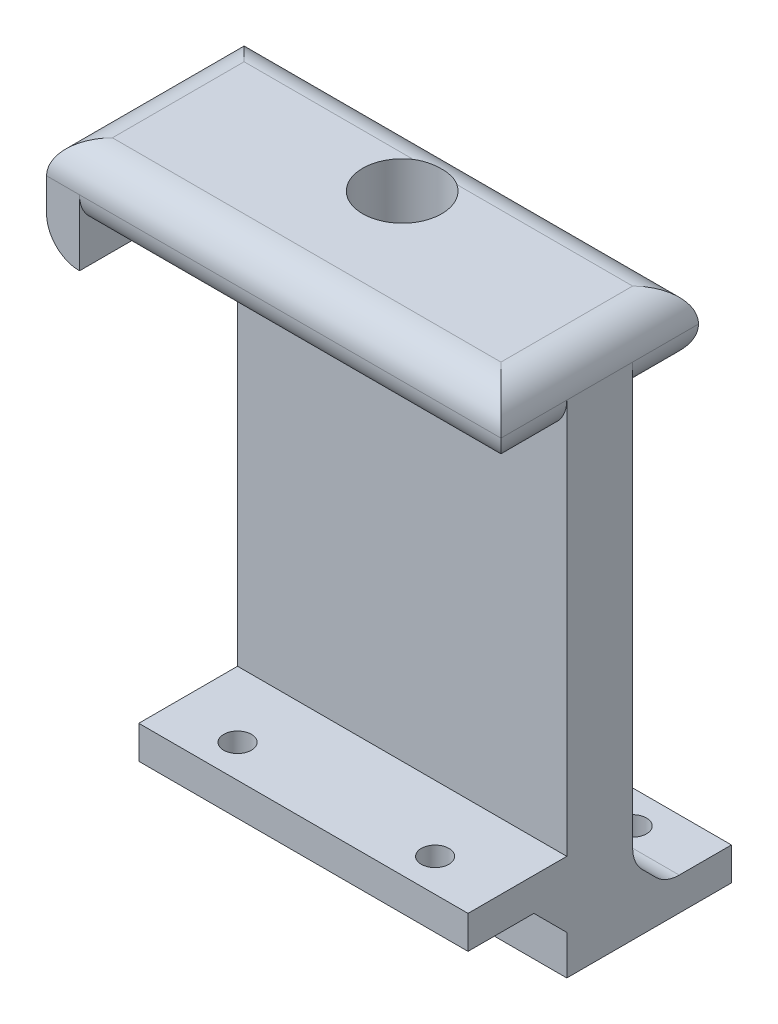
SolidWorks part; units mm, degrees
ref_plane "Plan de face" through (0, 0, 0) normal (0, 0, 1) x (1, 0, 0)
ref_plane "Plan de dessus" through (0, 0, 0) normal (0, 1, 0) x (1, 0, 0)
ref_plane "Plan de droite" through (0, 0, 0) normal (1, 0, 0) x (0, 0, -1)
sketch "Esquisse1" plane through (0, 0, 0) normal (0, 0, 1) x (1, 0, 0)
  line L0 (0, 0) -> (0, 81)
  line L1 (0, 81) -> (-69, 81)
  line L2 (-69, 81) -> (-69, 66)
  line L3 (-69, 66) -> (-64, 66)
  line L4 (-64, 66) -> (-64, 71)
  line L5 (-64, 71) -> (-50, 71)
  line L6 (-50, 71) -> (-50, 0)
  line L7 (-50, 0) -> (0, 0)
  dimension "D1" = 71
  dimension "D2" = 14
  dimension "D3" = 5
  dimension "D4" = 5
  dimension "D5" = 10
  dimension "D6" = 50
extrude "Boss.-Extru.1" add sketch "Esquisse1" along normal blind 10
sketch "Esquisse2" plane through (0, 0, 10) normal (0, 0, 1) x (1, 0, 0)
  line L0 (0, 0) -> (0, 81) construction
  line L1 (0, 71) -> (-69, 71)
  line L2 (0, 71) -> (0, 81)
  line L3 (0, 81) -> (-69, 81)
  line L4 (-69, 71) -> (-69, 81)
  line L5 (-64, 71) -> (-50, 71) construction
  dimension "D1" = 0
extrude "Boss.-Extru.2" add sketch "Esquisse2" along normal blind 10 and the other way blind 20
sketch "Esquisse3" plane through (0, 0, 0) normal (0, 0, -1) x (-1, 0, 0)
  line L0 (0, 0) -> (0, 71) construction
  line L1 (50, 0) -> (0, 0)
  line L2 (50, 0) -> (50, 5)
  line L3 (50, 5) -> (0, 5)
  line L4 (0, 0) -> (0, 5)
  dimension "D1" = 5
extrude "Boss.-Extru.3" add sketch "Esquisse3" along normal blind 15
chamfer "Chanfrein1" distance 5 angle 45 1 edges at (-25, 5, 0)
sketch "Esquisse4" plane through (0, 5, 0) normal (0, 1, 0) x (1, 0, 0)
  line L0 (-50, 10) -> (0, 10) construction
  line L2 (-50, 15) -> (-50, 5) construction
  line L3 (0, 15) -> (0, 5) construction
  circle A0 centre (-40, 10) radius 2.1
  circle A1 centre (-10, 10) radius 2.1
  dimension "D1" = 10
  dimension "D2" = 10
  dimension "D3" = 4.2
  dimension "D4" = 4.2
extrude "Enlèv. mat.-Extru.1" cut sketch "Esquisse4" against normal blind 15
sketch "Esquisse5" plane through (-69, 0, 0) normal (-1, 0, 0) x (0, 0, 1)
  line L0 (10, 66) -> (0, 66) construction
  line L1 (20, 71) -> (-10, 71)
  line L2 (20, 71) -> (20, 66)
  line L3 (20, 66) -> (-10, 66)
  line L4 (-10, 71) -> (-10, 66)
  line L5 (-10, 81) -> (-10, 71) construction
  dimension "D1" = 0
  dimension "D2" = 0
extrude "Boss.-Extru.4" add sketch "Esquisse5" against normal up to surface (5 mm away) up to face at (-64, 68.5, 5)
sketch "Esquisse6" plane through (0, 0, 10) normal (0, 0, 1) x (1, 0, 0)
  line L0 (0, 0) -> (0, 71) construction
  line L1 (0, 11) -> (-50, 11)
  line L2 (0, 11) -> (0, 16)
  line L3 (0, 16) -> (-50, 16)
  line L4 (-50, 11) -> (-50, 16)
  line L5 (-50, 71) -> (-50, 0) construction
  line L6 (-50, 0) -> (0, 0) construction
  dimension "D1" = 11
  dimension "D2" = 5
extrude "Boss.-Extru.5" add sketch "Esquisse6" along normal blind 15
chamfer "Chanfrein2" distance 5 angle 45 1 edges at (-25, 11, 10)
sketch "Esquisse7" plane through (0, 11, 0) normal (0, -1, 0) x (1, 0, 0)
  line L0 (0, 20) -> (-50, 20) construction
  line L1 (0, 25) -> (0, 15) construction
  line L2 (-50, 25) -> (-50, 15) construction
  circle A0 centre (-10, 20) radius 2.1
  circle A1 centre (-40, 20) radius 2.1
  dimension "D1" = 4.2
  dimension "D2" = 4.2
  dimension "D3" = 10
  dimension "D4" = 10
extrude "Enlèv. mat.-Extru.2" cut sketch "Esquisse7" against normal blind 15
sketch "Esquisse8" plane through (0, 81, 0) normal (0, 1, 0) x (1, 0, 0)
  line L0 (0, 10) -> (-69, 10) construction
  line L1 (0, -20) -> (0, 10) construction
  circle A0 centre (-35, 0) radius 6
  dimension "D1" = 12
  dimension "D2" = 10
  dimension "D3" = 35
extrude "Enlèv. mat.-Extru.3" cut sketch "Esquisse8" against normal blind 20
fillet "Congé1" radius 5 11 edges at (-25, 10, 0) (-25, 5, -5) (-34.5, 81, 20) (-32, 71, 20) (0, 71, 15) (0, 71, -5) (0, 81, 5) (-32, 71, -10) (-34.5, 81, -10) (-69, 81, 5) (-69, 66, 5)
